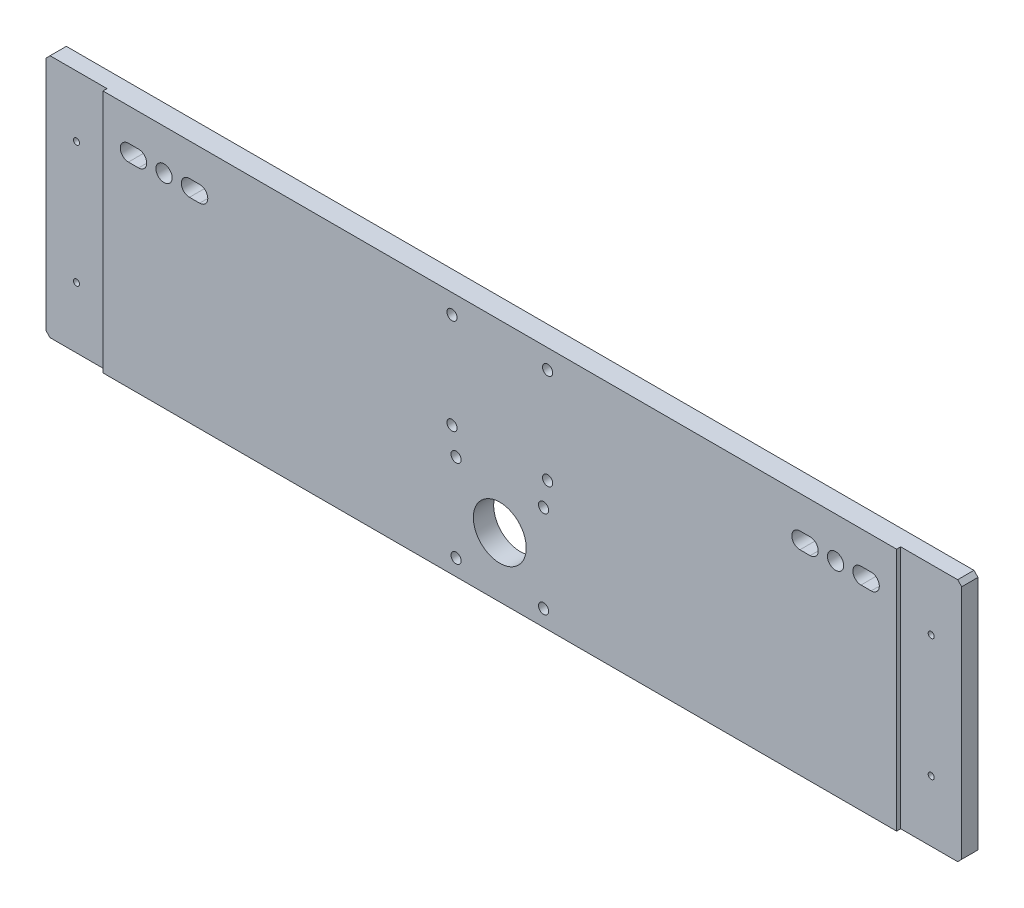
SolidWorks part; units mm, degrees
ref_plane "Piano frontale" through (0, 0, 0) normal (0, 0, 1) x (1, 0, 0)
ref_plane "Piano superiore" through (0, 0, 0) normal (0, 1, 0) x (1, 0, 0)
ref_plane "Piano destro" through (0, 0, 0) normal (1, 0, 0) x (0, 0, -1)
sketch "Schizzo1" plane through (0, 0, 0) normal (0, 0, 1) x (1, 0, 0)
  line L0 (225, 120) -> (225, 0) construction
  line L1 (2, 0) -> (448, 0)
  line L2 (0, 2) -> (0, 118)
  line L3 (2, 120) -> (448, 120)
  line L4 (450, 2) -> (450, 118)
  line L5 (203.5, 52.7163) -> (203.5, 5.9855) construction
  line L6 (250.0723, 51) -> (199.9971, 51) construction
  line L7 (225, 29.5) -> (243.5099, 29.5) construction
  line L8 (459.2931, 100) -> (370.8276, 100) construction
  line L9 (407.5, 100) -> (402.5, 100) construction
  line L10 (407.5, 96) -> (402.5, 96)
  line L11 (407.5, 104) -> (402.5, 104)
  line L12 (377.5, 100) -> (372.5, 100) construction
  line L13 (377.5, 96) -> (372.5, 96)
  line L14 (377.5, 104) -> (372.5, 104)
  line L15 (42.5, 100) -> (47.5, 100) construction
  line L16 (42.5, 96) -> (47.5, 96)
  line L17 (42.5, 104) -> (47.5, 104)
  line L18 (72.5, 100) -> (77.5, 100) construction
  line L19 (72.5, 96) -> (77.5, 96)
  line L20 (72.5, 104) -> (77.5, 104)
  line L21 (0, 118) -> (2, 120)
  line L22 (2, 0) -> (0, 2)
  line L23 (448, 0) -> (450, 2)
  line L24 (448, 120) -> (450, 118)
  line L25 (225, 60) -> (450, 60) construction
  line L26 (201.5, 87) -> (258.1315, 87) construction
  circle A0 centre (225, 29.5) radius 13
  arc A1 (407.5, 96) -> (407.5, 104) centre (407.5, 100) ccw
  arc A2 (402.5, 104) -> (402.5, 96) centre (402.5, 100) ccw
  circle A3 centre (390, 100) radius 4
  arc A4 (377.5, 96) -> (377.5, 104) centre (377.5, 100) ccw
  arc A5 (372.5, 104) -> (372.5, 96) centre (372.5, 100) ccw
  arc A6 (42.5, 96) -> (42.5, 104) centre (42.5, 100) cw
  arc A7 (47.5, 104) -> (47.5, 96) centre (47.5, 100) cw
  arc A8 (72.5, 96) -> (72.5, 104) centre (72.5, 100) cw
  arc A9 (77.5, 104) -> (77.5, 96) centre (77.5, 100) cw
  circle A10 centre (60, 100) radius 4
  circle A11 centre (15, 30) radius 1.5
  circle A12 centre (435, 30) radius 1.5
  circle A13 centre (203.5, 51) radius 2.5
  circle A14 centre (246.5, 51) radius 2.5
  circle A15 centre (246.5, 8) radius 2.5
  circle A16 centre (203.5, 8) radius 2.5
  circle A17 centre (435, 90) radius 1.5
  circle A18 centre (15, 90) radius 1.5
  circle A19 centre (248.5, 110.5) radius 2.5
  circle A20 centre (248.5, 63.5) radius 2.5
  circle A21 centre (201.5, 110.5) radius 2.5
  circle A22 centre (201.5, 63.5) radius 2.5
  point P0 (0, 0)
  point P1 (450, 120)
  point P2 (0, 120)
  point P3 (450, 0)
  point P13 (203.5, 51)
  point P14 (246.5, 51)
  point P15 (203.5, 8)
  point P17 (246.5, 8)
  point P22 (405, 100)
  point P31 (375, 100)
  point P38 (45, 100)
  point P45 (75, 100)
  dimension "D4" = 26
  dimension "D10" = 8
  dimension "D15" = 3
  dimension "D17" = 5
  dimension "D24" = 5
  dimension "D1" = 120
  dimension "D2" = 450
  dimension "D3" = 90.5
  dimension "D5" = 21.5
  dimension "D6" = 21.5
  dimension "D7" = 20
  dimension "D8" = 5
  dimension "D9" = 8
  dimension "D11" = 45
  dimension "D12" = 60
  dimension "D13" = 75
  dimension "D14" = 30
  dimension "D16" = 15
  dimension "D18" = 33
  dimension "D23" = 23.5
  dimension "D25" = 23.5
extrude "Estrusione-Estrusione1" add sketch "Schizzo1" against normal blind 10
sketch "Schizzo2" plane through (0, 0, 0) normal (0, 0, 1) x (1, 0, 0)
  line L0 (448, 120) -> (2, 120) construction
  line L1 (30, 120) -> (0, 120)
  line L2 (30, 120) -> (30, 0)
  line L3 (30, 0) -> (0, 0)
  line L4 (0, 120) -> (0, 0)
  line L5 (225, 120) -> (225, -23.5993) construction
  line L6 (450, 120) -> (450, 0)
  line L7 (420, 0) -> (450, 0)
  line L8 (420, 120) -> (420, 0)
  line L9 (420, 120) -> (450, 120)
  dimension "D1" = 30
extrude "Taglio-Estrusione1" cut sketch "Schizzo2" against normal blind 2
